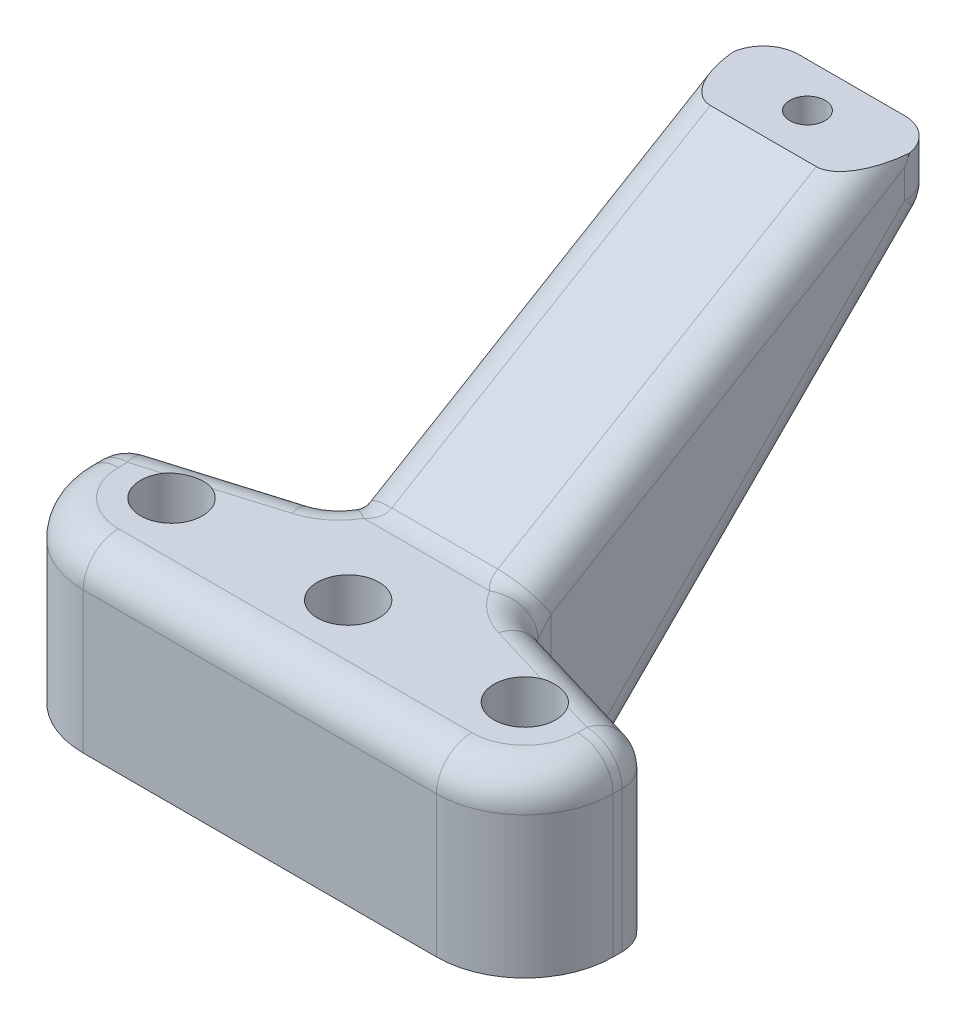
SolidWorks part; units mm, degrees
material "ABS PC"
ref_plane "Front Plane" through (0, 0, 0) normal (0, 0, 1) x (1, 0, 0)
ref_plane "Top Plane" through (0, 0, 0) normal (0, 1, 0) x (1, 0, 0)
ref_plane "Right Plane" through (0, 0, 0) normal (1, 0, 0) x (0, 0, -1)
sketch "Sketch1" plane through (0, 0, 0) normal (1, 0, 0) x (0, 0, -1)
  line L0 (0, 0) -> (0, 10)
  line L1 (0, 11.55) -> (0, -11.55) construction
  line L2 (28.5, 21) -> (10, 10)
  line L3 (33.5, 21) -> (33.5, 18)
  line L4 (28.5, 21) -> (33.5, 21)
  line L5 (33.5, 18) -> (15.5, 0)
  line L6 (10, 10) -> (0, 10)
  line L7 (15.5, 0) -> (0, 0)
  dimension "D1" = 33.5
  dimension "D2" = 10
  dimension "D3" = 21
  dimension "D4" = 5
  dimension "D5" = 10
  dimension "D6" = 18
  dimension "D7" = 45
extrude "Boss-Extrude1" add sketch "Sketch1" along normal mid plane 30
sketch "Sketch2" plane through (0, 0, 0) normal (0, 1, 0) x (1, 0, 0)
  line L0 (5, 41.8414) -> (5, 10)
  line L1 (5, 10) -> (15, 7)
  line L2 (15, 7) -> (32.3436, 28.5251)
  line L3 (32.3436, 28.5251) -> (5, 41.8414)
  line L4 (0, 28.5) -> (0, 0) construction
  line L6 (-11.55, 0) -> (11.55, 0) construction
  line L7 (0, 32) -> (0, 30)
  line L8 (15, 10) -> (15, 0) construction
  line L9 (0, 3.25) -> (0, 6.75)
  line L10 (15, 28.5) -> (-15, 28.5) construction
  line L11 (15, 10) -> (-15, 10) construction
  line L12 (15, 33.5) -> (-15, 33.5) construction
  circle A0 centre (10, 5) radius 1.75
  arc A1 (0, 32) -> (0, 30) centre (0, 31) cw
  arc A2 (0, 6.75) -> (0, 3.25) centre (0, 5) cw
  dimension "D1" = 3.5
  dimension "D2" = 1
  dimension "D3" = 2.5
  dimension "D7" = 5
  dimension "D8" = 5
  dimension "D9" = 1.75
  dimension "D4" = 5
  dimension "D6" = 7
extrude "Cut-Extrude2" cut sketch "Sketch2" along normal blind 30
mirror "Mirror1" about plane through (0, 0, 0) normal (1, 0, 0) of "Cut-Extrude2"
fillet "Fillet1" radius 5 2 edges at (15, 5, 0) (-15, 5, 0)
fillet "Fillet2" radius 2 19 edges at (15, 10, -6) (13.5355, 10, -1.4645) (0, 10, 0) (-13.5355, 10, -1.4645) (5, 5, -10) (15, 5, -7) (-5, 5, -10) (-15, 5, -7) (0, 10, -10) (10, 10, -8.5) (-15, 10, -6) (-10, 10, -8.5) (5, 15.5, -19.25) (-5, 15.5, -19.25) (5, 19.5, -33.5) (-5, 19.5, -33.5) (0, 18, -33.5) (5, 9, -24.5) (-5, 9, -24.5)
